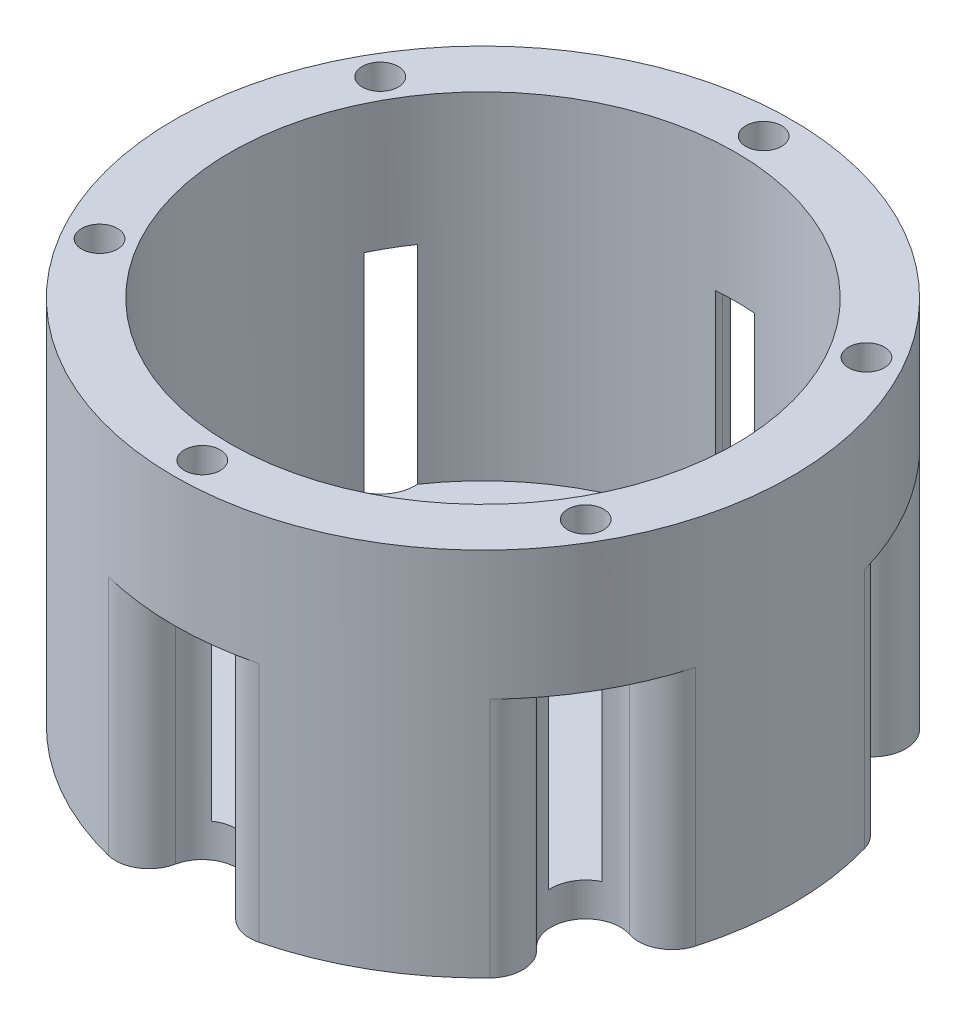
SolidWorks part; units mm, degrees
ref_plane "Front Plane" through (0, 0, 0) normal (0, 0, 1) x (1, 0, 0)
ref_plane "Top Plane" through (0, 0, 0) normal (0, 1, 0) x (1, 0, 0)
ref_plane "Right Plane" through (0, 0, 0) normal (1, 0, 0) x (0, 0, -1)
sketch "Sketch1" plane through (0, 0, 0) normal (0, 1, 0) x (1, 0, 0)
  circle A0 centre (0, 0) radius 27.5
  circle A1 centre (0, 0) radius 25 construction
  circle A2 centre (0, 25) radius 1.6
  circle A3 centre (21.6506, 12.5) radius 1.6
  circle A4 centre (21.6506, -12.5) radius 1.6
  circle A5 centre (0, -25) radius 1.6
  circle A6 centre (-21.6506, -12.5) radius 1.6
  circle A7 centre (-21.6506, 12.5) radius 1.6
  point P19 (0, 0)
  point P31 (0, 0)
  dimension "D1" = 55
  dimension "D2" = 50
  dimension "D3" = 3.2
  dimension "D4" = 6
extrude "Boss-Extrude1" add sketch "Sketch1" along normal blind 33
sketch "Sketch2" plane through (0, 33, 0) normal (0, 1, 0) x (1, 0, 0)
  circle A0 centre (0, 0) radius 22.5
  dimension "D1" = 45
extrude "Cut-Extrude1" cut sketch "Sketch2" against normal blind 30
sketch "Sketch3" plane through (0, 0, 0) normal (0, -1, 0) x (1, 0, 0)
  circle A0 centre (0, 25) radius 3.1
  dimension "D1" = 6.2
extrude "Cut-Extrude2" cut sketch "Sketch3" against normal blind 21.5
fillet "Fillet1" radius 3 2 edges at (-1.9213, 10.75, 27.4328) (1.9213, 10.75, 27.4328)
pattern_circular "CirPattern1" count 6 over 360 about axis through (0, 33, 0) along (0, -1, 0) of "Cut-Extrude2", "Fillet1" reverse direction yes
sketch "Sketch5" plane through (0, 0, 0) normal (0, -1, 0) x (1, 0, 0)
  line L1 (-8, -8) -> (8, -8) construction
  line L2 (-8, -8) -> (-8, 8) construction
  line L3 (-8, 8) -> (8, 8) construction
  line L4 (8, -8) -> (8, 8) construction
  line L5 (-8, -8) -> (8, 8) construction
  line L6 (-8, 8) -> (8, -8) construction
  circle A0 centre (-8, 8) radius 1.6
  circle A1 centre (8, 8) radius 1.6
  circle A2 centre (8, -8) radius 1.6
  circle A3 centre (-8, -8) radius 1.6
  point P0 (0, 0)
  dimension "D3" = 3.2
  dimension "D1" = 16
  dimension "D2" = 16
extrude "Cut-Extrude3" cut sketch "Sketch5" against normal blind 10
